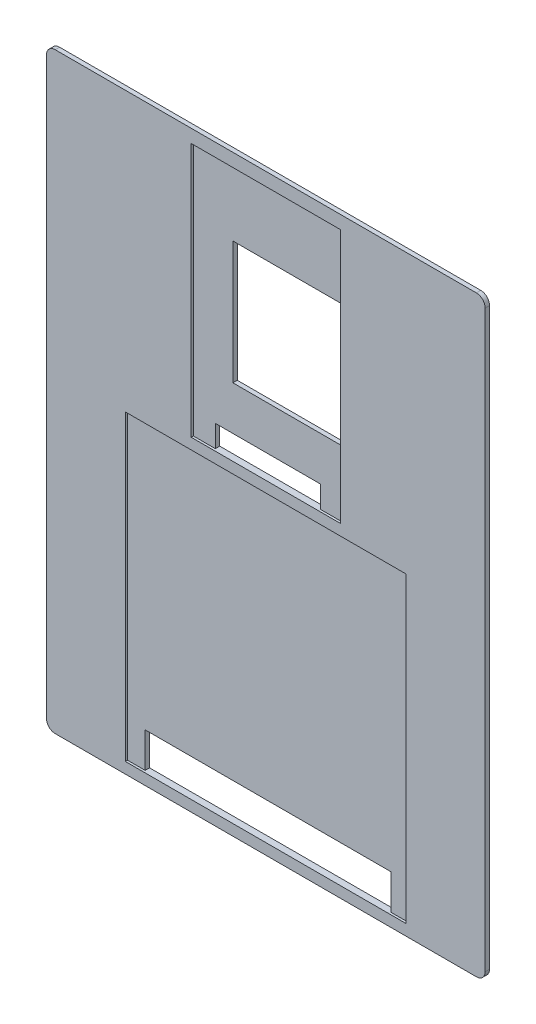
SolidWorks part; units mm, degrees
ref_plane "Front Plane" through (0, 0, 0) normal (0, 0, 1) x (1, 0, 0)
ref_plane "Top Plane" through (0, 0, 0) normal (0, 1, 0) x (1, 0, 0)
ref_plane "Right Plane" through (0, 0, 0) normal (1, 0, 0) x (0, 0, -1)
sketch "Sketch1" plane through (0, 0, 0) normal (0, 0, 1) x (1, 0, 0)
  line L0 (0, -67.5) -> (0, -30.5)
  line L1 (-50, 67.5) -> (50, 67.5)
  line L2 (-50, 67.5) -> (-50, -67.5)
  line L3 (-50, -67.5) -> (50, -67.5)
  line L4 (50, 67.5) -> (50, -67.5)
  line L5 (-50, 67.5) -> (50, -67.5) construction
  line L6 (-50, -67.5) -> (50, 67.5) construction
  line L7 (0, 67.5) -> (0, 35.5)
  line L8 (17, 64.5) -> (17, 49.5)
  line L9 (-17, 64.5) -> (17, 64.5)
  line L10 (-17, 64.5) -> (-17, 6.5)
  line L11 (-17, 6.5) -> (17, 6.5)
  line L12 (17, 64.5) -> (17, 6.5)
  line L13 (-17, 64.5) -> (17, 6.5) construction
  line L14 (-17, 6.5) -> (17, 64.5) construction
  line L15 (-32, 4) -> (32, 4)
  line L16 (-32, 4) -> (-32, -65)
  line L17 (-32, -65) -> (32, -65)
  line L18 (32, 4) -> (32, -65)
  line L19 (-32, 4) -> (32, -65) construction
  line L20 (-32, -65) -> (32, 4) construction
  line L21 (17, 49.5) -> (-8, 49.5)
  line L22 (-8, 49.5) -> (-8, 21.5)
  line L23 (-8, 21.5) -> (17, 21.5)
  line L24 (0, 6.5) -> (12, 6.5)
  line L25 (12, 6.5) -> (12, 11.5)
  line L26 (0, 6.5) -> (-12, 6.5)
  line L27 (-12, 6.5) -> (-12, 11.5)
  line L28 (-12, 11.5) -> (12, 11.5)
  line L29 (0, -65) -> (28, -65)
  line L30 (28, -65) -> (28, -57)
  line L31 (28, -57) -> (-28, -57)
  line L32 (-28, -57) -> (-28, -65)
  line L33 (-28, -65) -> (0, -65)
  point P0 (0, 0)
  dimension "D1" = 135
  dimension "D2" = 100
  dimension "D3" = 37
  dimension "D4" = 32
  dimension "D5" = 58
  dimension "D6" = 34
  dimension "D7" = 69
  dimension "D8" = 64
  dimension "D9" = 15
  dimension "D10" = 25
  dimension "D11" = 28
  dimension "D12" = 12
  dimension "D13" = 5
  dimension "D14" = 12
  dimension "D15" = 5
  dimension "D16" = 28
  dimension "D17" = 8
  dimension "D18" = 56
extrude "Boss-Extrude2" add sketch "Sketch1" along normal blind 1.5 contours L15 L18 L17 L3 L4 L1 L9 L8 L12 L11 L10 L2 L16 region at (-25, -65.82, 0)
extrude "Boss-Extrude3" add sketch "Sketch1<5>" along normal blind 1 contours L32 L31 L30 L17 L18 L15 L16 | L27 L28 L25 L11 L12 L23 L22 L21 L7 L9 L10 | L21 L8 L9 L7 region at (8.5, 57, 0) region at (-0.6723, 57, 0) region at (0, -27.0565, 0)
sketch "Sketch1<5>" plane through (0, 0, 0) normal (0, 0, 1) x (1, 0, 0) same geometry as "Sketch1"
fillet "Fillet1" radius 2 4 edges at (50, 67.5, 0.75) (-50, 67.5, 0.75) (50, -67.5, 0.75) (-50, -67.5, 0.75)
sketch "Sketch2" plane through (0, 0, 0) normal (0, 0, -1) x (-1, 0, 0)
  line L0 (-17, 64.5) -> (-17, 49.5) construction
  line L1 (-49, 66.5) -> (49, 66.5)
  line L2 (-49, 66.5) -> (-49, -66.5)
  line L3 (-49, -66.5) -> (49, -66.5)
  line L4 (49, 66.5) -> (49, -66.5)
  line L5 (-49, 66.5) -> (49, -66.5) construction
  line L6 (-49, -66.5) -> (49, 66.5) construction
  line L7 (-17, 49.5) -> (8, 49.5) construction
  line L8 (8, 49.5) -> (8, 21.5) construction
  line L9 (8, 21.5) -> (-17, 21.5) construction
  line L10 (0, 67.5) -> (0, 35.5) construction
  line L11 (0, -67.5) -> (0, -30.5) construction
  line L12 (17, 64.5) -> (-17, 64.5) construction
  line L13 (17, 64.5) -> (17, 6.5) construction
  line L14 (17, 6.5) -> (-17, 6.5) construction
  line L15 (-17, 64.5) -> (-17, 6.5) construction
  line L16 (50, 67.5) -> (-50, 67.5) construction
  line L17 (-50, 67.5) -> (-50, -67.5) construction
  line L18 (50, -67.5) -> (-50, -67.5) construction
  line L19 (50, 67.5) -> (50, -67.5) construction
  line L20 (0, -65) -> (-28, -65) construction
  line L21 (-28, -65) -> (-28, -57) construction
  line L22 (-28, -57) -> (28, -57) construction
  line L23 (28, -57) -> (28, -65) construction
  line L24 (28, -65) -> (0, -65) construction
  line L25 (0, 6.5) -> (-12, 6.5) construction
  line L26 (-12, 6.5) -> (-12, 11.5) construction
  line L27 (12, 11.5) -> (-12, 11.5) construction
  line L28 (12, 6.5) -> (12, 11.5) construction
  line L29 (0, 6.5) -> (12, 6.5) construction
  line L30 (32, 4) -> (-32, 4) construction
  line L31 (32, 4) -> (32, -65) construction
  line L32 (32, -65) -> (-32, -65) construction
  line L33 (-32, 4) -> (-32, -65) construction
  line L34 (-17, 64.5) -> (-17, 49.5)
  line L35 (-17, 49.5) -> (8, 49.5)
  line L36 (8, 49.5) -> (8, 21.5)
  line L37 (8, 21.5) -> (-17, 21.5)
  line L38 (0, 67.5) -> (0, 35.5)
  line L39 (0, -67.5) -> (0, -30.5)
  line L40 (17, 64.5) -> (-17, 64.5)
  line L41 (17, 64.5) -> (17, 6.5)
  line L42 (17, 6.5) -> (-17, 6.5)
  line L43 (-17, 64.5) -> (-17, 6.5)
  line L44 (50, 67.5) -> (-50, 67.5)
  line L45 (-50, 67.5) -> (-50, -67.5)
  line L46 (50, -67.5) -> (-50, -67.5)
  line L47 (50, 67.5) -> (50, -67.5)
  line L48 (0, -65) -> (-28, -65)
  line L49 (-28, -65) -> (-28, -57)
  line L50 (-28, -57) -> (28, -57)
  line L51 (28, -57) -> (28, -65)
  line L52 (28, -65) -> (0, -65)
  line L53 (0, 6.5) -> (-12, 6.5)
  line L54 (-12, 6.5) -> (-12, 11.5)
  line L55 (12, 11.5) -> (-12, 11.5)
  line L56 (12, 6.5) -> (12, 11.5)
  line L57 (0, 6.5) -> (12, 6.5)
  line L58 (32, 4) -> (-32, 4)
  line L59 (32, 4) -> (32, -65)
  line L60 (32, -65) -> (-32, -65)
  line L61 (-32, 4) -> (-32, -65)
  point P0 (0, 0)
  line M25 (48, 67.5) -> (-48, 67.5)
  arc M26 (-48, 67.5) -> (-50, 65.5) centre (-48, 65.5) ccw
  line M27 (-50, 65.5) -> (-50, -65.5)
  arc M28 (-50, -65.5) -> (-48, -67.5) centre (-48, -65.5) ccw
  line M29 (-48, -67.5) -> (48, -67.5)
  arc M30 (48, -67.5) -> (50, -65.5) centre (48, -65.5) ccw
  line M31 (50, -65.5) -> (50, 65.5)
  arc M32 (50, 65.5) -> (48, 67.5) centre (48, 65.5) ccw
  dimension "D1" = 133
  dimension "D2" = 98
extrude "Cut-Extrude1" cut sketch "Sketch2" against normal blind 0.5 contours L39 L3 L2 L1 L38 M29 M25 M26 M27 M28 | L39 L38 L1 L4 L3 M29 M30 M31 M32 M25 region at (49.144, 0, 0) region at (-1.4396, 67, 0)
fillet "Fillet2" radius 2 4 edges at (49, -66.5, 0.25) (-49, -66.5, 0.25) (-49, 66.5, 0.25) (49, 66.5, 0.25)
